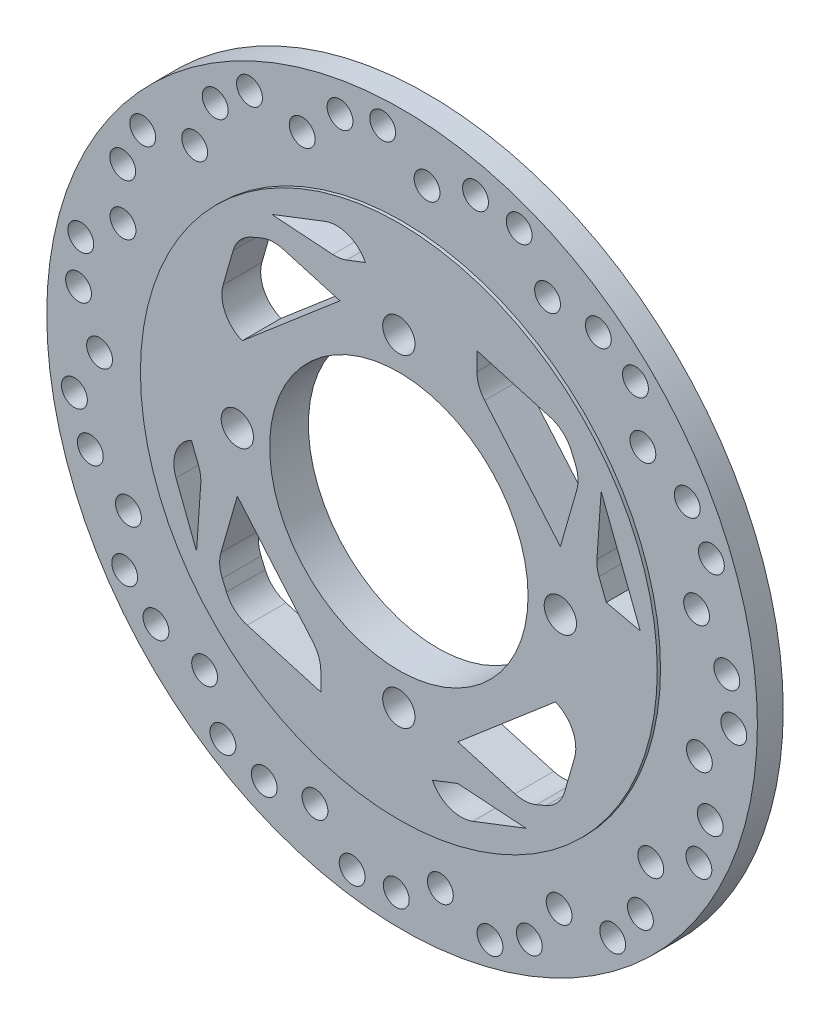
SolidWorks part; units mm, degrees
material "Cast Alloy Steel"
ref_plane "Front Plane" through (0, 0, 0) normal (0, 0, 1) x (1, 0, 0)
ref_plane "Top Plane" through (0, 0, 0) normal (0, 1, 0) x (1, 0, 0)
ref_plane "Right Plane" through (0, 0, 0) normal (1, 0, 0) x (0, 0, -1)
sketch "Sketch1" plane through (0, 0, 0) normal (0, 0, 1) x (1, 0, 0)
  line L0 (-39.3529, 62.6179) -> (-7.9825, 74.7292)
  line L1 (-7.9825, 74.7292) -> (-10.3651, 64.2063)
  line L2 (-10.3651, 64.2063) -> (-18.238, 61.1667)
  line L3 (-39.3529, 62.6179) -> (-18.238, 61.1667)
  line L4 (-39.3529, 56.0659) -> (-18.238, 50)
  line L5 (-39.3529, 56.0659) -> (-50, 51.4993)
  line L6 (-50, 51.4993) -> (-57.8521, 24.1668)
  line L7 (-57.8521, 24.1668) -> (-48.486, 24.1668)
  line L8 (-48.486, 24.1668) -> (-18.238, 50)
  line L9 (62.6179, 39.3529) -> (61.1667, 18.238)
  line L10 (64.2063, 10.3651) -> (61.1667, 18.238)
  line L11 (74.7292, 7.9825) -> (64.2063, 10.3651)
  line L12 (62.6179, 39.3529) -> (74.7292, 7.9825)
  line L13 (24.1668, 48.486) -> (50, 18.238)
  line L14 (56.0659, 39.3529) -> (50, 18.238)
  line L15 (56.0659, 39.3529) -> (51.4993, 50)
  line L16 (51.4993, 50) -> (24.1668, 57.8521)
  line L17 (24.1668, 57.8521) -> (24.1668, 48.486)
  line L18 (39.3529, -62.6179) -> (18.238, -61.1667)
  line L19 (10.3651, -64.2063) -> (18.238, -61.1667)
  line L20 (7.9825, -74.7292) -> (10.3651, -64.2063)
  line L21 (39.3529, -62.6179) -> (7.9825, -74.7292)
  line L22 (48.486, -24.1668) -> (18.238, -50)
  line L23 (39.3529, -56.0659) -> (18.238, -50)
  line L24 (39.3529, -56.0659) -> (50, -51.4993)
  line L25 (50, -51.4993) -> (57.8521, -24.1668)
  line L26 (57.8521, -24.1668) -> (48.486, -24.1668)
  line L27 (-62.6179, -39.3529) -> (-61.1667, -18.238)
  line L28 (-64.2063, -10.3651) -> (-61.1667, -18.238)
  line L29 (-74.7292, -7.9825) -> (-64.2063, -10.3651)
  line L30 (-62.6179, -39.3529) -> (-74.7292, -7.9825)
  line L31 (-24.1668, -48.486) -> (-50, -18.238)
  line L32 (-56.0659, -39.3529) -> (-50, -18.238)
  line L33 (-56.0659, -39.3529) -> (-51.4993, -50)
  line L34 (-51.4993, -50) -> (-24.1668, -57.8521)
  line L35 (-24.1668, -57.8521) -> (-24.1668, -48.486)
  circle A0 centre (0, 0) radius 110
  circle A1 centre (0, 0) radius 80
  circle A2 centre (0, 0) radius 40
  circle A3 centre (0, 50) radius 5
  circle A4 centre (50, 0) radius 5
  circle A5 centre (0, -50) radius 5
  circle A6 centre (-50, 0) radius 5
  circle A7 centre (-80.2906, 64.2063) radius 4
  circle A8 centre (-64.2063, 68.2063) radius 4
  circle A9 centre (-57.8521, 82.6855) radius 4
  circle A10 centre (-19.2193, 99.0675) radius 4
  circle A11 centre (-30.9134, 88.4246) radius 4
  circle A12 centre (-47.2341, 91.3125) radius 4
  circle A13 centre (22.7367, 98.3198) radius 4
  circle A14 centre (7.7248, 93.3534) radius 4
  circle A15 centre (-6.0104, 102.6299) radius 4
  circle A16 centre (60.7613, 80.5718) radius 4
  circle A17 centre (45.0272, 82.1407) radius 4
  circle A18 centre (36.2526, 96.2017) radius 4
  circle A19 centre (88.2797, 48.8921) radius 4
  circle A20 centre (74.544, 56.725) radius 4
  circle A21 centre (72.2472, 73.1394) radius 4
  circle A22 centre (100.5337, 8.7586) radius 4
  circle A23 centre (91.1715, 21.5011) radius 4
  circle A24 centre (95.7496, 37.4306) radius 4
  circle A25 centre (95.4046, -32.8894) radius 4
  circle A26 centre (92.0346, -17.4405) radius 4
  circle A27 centre (102.696, -4.7503) radius 4
  circle A28 centre (73.7791, -68.8505) radius 4
  circle A29 centre (76.9841, -53.3666) radius 4
  circle A30 centre (91.8853, -46.1098) radius 4
  circle A31 centre (39.3966, -92.9067) radius 4
  circle A32 centre (48.6223, -80.065) radius 4
  circle A33 centre (65.1868, -79.4966) radius 4
  circle A34 centre (-1.798, -100.8985) radius 4
  circle A35 centre (11.8533, -92.9195) radius 4
  circle A36 centre (27.217, -99.1376) radius 4
  circle A37 centre (-42.6817, -91.4441) radius 4
  circle A38 centre (-26.9652, -89.7074) radius 4
  circle A39 centre (-15.4589, -101.6368) radius 4
  circle A40 centre (-76.1853, -66.1781) radius 4
  circle A41 centre (-61.1212, -70.984) radius 4
  circle A42 centre (-55.4619, -86.5622) radius 4
  circle A43 centre (-96.5158, -29.4694) radius 4
  circle A44 centre (-84.7088, -39.9869) radius 4
  circle A45 centre (-85.8749, -56.5201) radius 4
  circle A46 centre (-100.1579, 12.3349) radius 4
  circle A47 centre (-93.6495, -2.0757) radius 4
  circle A48 centre (-101.4395, -16.7052) radius 4
  circle A49 centre (-86.4817, 52.0064) radius 4
  circle A50 centre (-86.3973, 36.1945) radius 4
  circle A51 centre (-99.4642, 25.9982) radius 4
  point P16 (0, 0)
  point P53 (0, 0)
  point P144 (0, 0)
  dimension "D1" = 4
  dimension "D3" = 15
  dimension "D2" = 4
extrude "Boss-Extrude3" add sketch "Sketch1" against normal blind 10 and the other way blind 2 contours A1 A6 A5 A4 A3 A2 L35 L34 L33 L32 L31 L26 L25 L24 L23 L22 L17 L16 L15 L14 L13 L8 L7 L6 L5 L4 L3 L0 L1 L2 L9 L12 L11 L10 L18 L21 L20 L19 region at (-77.7373, 0, 0)
extrude "Boss-Extrude4" add sketch "Sketch1<6>" against normal blind 7 and the other way blind 1 contours A0 A51 A50 A49 A48 A47 A46 A45 A44 A43 A42 A41 A40 A39 A38 A37 A36 A35 A34 A33 A32 A31 A30 A29 A28 A27 region at (-106.8887, 0, 0)
sketch "Sketch1<6>" plane through (0, 0, 0) normal (0, 0, 1) x (1, 0, 0) same geometry as "Sketch1"
fillet "Fillet1" radius 10 18 edges at (61.1667, 18.238, -4) (7.9825, -74.7292, -4) (-61.1667, -18.238, -4) (-51.4993, -50, -4) (-57.8521, 24.1668, -4) (-18.238, 61.1667, -4) (24.1668, 48.486, -4) (39.3529, -56.0659, -4) (51.4993, 50, -4) (56.0659, 39.3529, -4) (50, -51.4993, -4) (-56.0659, -39.3529, -4) (-50, 51.4993, -4) (-39.3529, 56.0659, -4) (-7.9825, 74.7292, -4) (57.8521, -24.1668, -4) (-24.1668, -48.486, -4) (-74.7292, -7.9825, -4)
